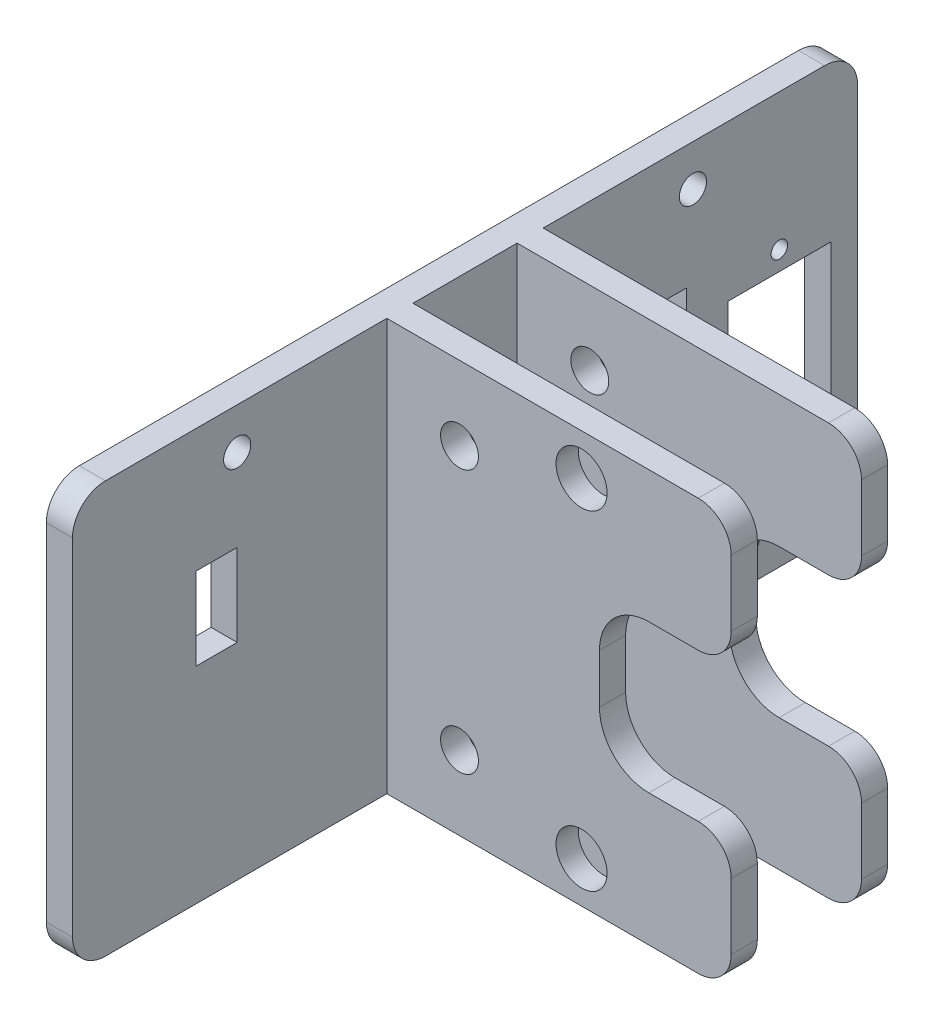
SolidWorks part; units mm, degrees
ref_plane "Front Plane" through (0, 0, 0) normal (0, 0, 1) x (1, 0, 0)
ref_plane "Top Plane" through (0, 0, 0) normal (0, 1, 0) x (1, 0, 0)
ref_plane "Right Plane" through (0, 0, 0) normal (1, 0, 0) x (0, 0, -1)
sketch "Sketch1" plane through (0, 0, 0) normal (0, 1, 0) x (1, 0, 0)
  line L0 (0, 9.5) -> (0, -9.5)
  line L5 (0, -9.5) -> (45, -9.5)
  line L6 (45, -9.5) -> (45, -6.325)
  line L17 (45, -6.325) -> (3.175, -6.325)
  line L18 (3.175, -6.325) -> (3.175, 6.325)
  line L19 (0, 0) -> (39.6882, 0) construction
  line L20 (45, 6.325) -> (3.175, 6.325)
  line L21 (45, 9.5) -> (45, 6.325)
  line L22 (0, 9.5) -> (45, 9.5)
  point P9 (3.175, 0)
  dimension "D1" = 19
  dimension "D2" = 3.175
  dimension "D3" = 3.175
  dimension "D4" = 45
extrude "Boss-Extrude1" add sketch "Sketch1" along normal blind 50
sketch "Sketch3" plane through (0, 0, 9.5) normal (0, 0, 1) x (1, 0, 0)
  line L1 (45, 50) -> (45, 0) construction
  line L2 (0, 50) -> (45, 50) construction
  line L3 (45, 25) -> (0, 25) construction
  line L4 (0, 50) -> (0, 0) construction
  circle A0 centre (26.825, 45) radius 3.1
  circle A2 centre (26.825, 5) radius 3.1
  dimension "D1" = 6.2
  dimension "D2" = 5
  dimension "D3" = 18.175
extrude "Cut-Extrude1" cut sketch "Sketch3" against normal blind 2.7
sketch "Sketch4" plane through (0, 0, -9.5) normal (0, 0, -1) x (-1, 0, 0)
  line L1 (-45, 50) -> (-45, 0) construction
  line L2 (0, 50) -> (-45, 50) construction
  line L3 (-45, 25) -> (0, 25) construction
  line L4 (0, 50) -> (0, 0) construction
  circle A0 centre (-26.825, 45) radius 3.1
  circle A2 centre (-26.825, 5) radius 3.1
  dimension "D4" = 6.2
  dimension "D1" = 5
  dimension "D2" = 18.175
extrude "Cut-Extrude2" cut sketch "Sketch4" against normal blind 2.7
fillet "Fillet1" radius 4 4 edges at (45, 50, 7.9125) (45, 50, -7.9125) (45, 0, -7.9125) (45, 0, 7.9125)
sketch "Sketch5" plane through (0, 0, 9.5) normal (0, 0, 1) x (1, 0, 0)
  line L0 (0, 25) -> (45, 25) construction
  line L1 (0, 50) -> (0, 0) construction
  line L2 (45, 46) -> (45, 4) construction
  circle A0 centre (12, 9) radius 2.3
  circle A1 centre (12, 41) radius 2.3
  dimension "D3" = 4.6
  dimension "D1" = 16
  dimension "D2" = 16
  dimension "D4" = 12
extrude "Cut-Extrude3" cut sketch "Sketch5" against normal up to surface (19 mm away) up to face at (23.725, 45, -9.5)
sketch "Sketch6" plane through (0, 0, 9.5) normal (0, 0, 1) x (1, 0, 0)
  line L0 (0, 0) -> (41, 0) construction
  line L1 (0, 50) -> (3.175, 50)
  line L2 (0, 50) -> (0, 0)
  line L3 (0, 0) -> (3.175, 0)
  line L4 (3.175, 50) -> (3.175, 0)
  dimension "D1" = 3.175
extrude "Boss-Extrude2" add sketch "Sketch6" along normal blind 38.175
sketch "Sketch7" plane through (0, 0, -9.5) normal (0, 0, -1) x (-1, 0, 0)
  line L0 (-41, 50) -> (0, 50) construction
  line L1 (0, 0) -> (-3.175, 0)
  line L2 (0, 0) -> (0, 50)
  line L3 (0, 50) -> (-3.175, 50)
  line L4 (-3.175, 0) -> (-3.175, 50)
  dimension "D1" = 3.175
extrude "Boss-Extrude3" add sketch "Sketch7" along normal blind 38.175
fillet "Fillet2" radius 4 4 edges at (1.5875, 0, -47.675) (1.5875, 50, -47.675) (1.5875, 0, 47.675) (1.5875, 50, 47.675)
sketch "Sketch10" plane through (0, 0, 0) normal (-1, 0, 0) x (0, 0, 1)
  line L0 (-47.675, 4) -> (-47.675, 46) construction
  line L3 (-43.675, 0) -> (43.675, 0) construction
  line L5 (-31.925, 31.075) -> (-44.425, 31.075)
  line L6 (-31.925, 31.075) -> (-31.925, 8.325)
  line L7 (-31.925, 8.325) -> (-44.425, 8.325)
  line L8 (-44.425, 31.075) -> (-44.425, 8.325)
  circle A0 centre (-38.175, 6) radius 1
  circle A1 centre (-38.175, 33.4) radius 1
  dimension "D1" = 2
  dimension "D2" = 27.4
  dimension "D3" = 9.5
  dimension "D4" = 6
  dimension "D5" = 12.5
  dimension "D6" = 22.75
  dimension "D7" = 2.325
  dimension "D8" = 6.25
extrude "Cut-Extrude7" cut sketch "Sketch10" against normal up to surface (3.175 mm away) up to face at (3.175, 25, -33.8928)
sketch "Sketch11" plane through (0, 0, 0) normal (-1, 0, 0) x (0, 0, 1)
  line L0 (-47.675, 25) -> (47.675, 25) construction
  line L1 (-47.675, 4) -> (-47.675, 46) construction
  line L2 (47.675, 46) -> (47.675, 4) construction
  line L3 (-43.675, 50) -> (43.675, 50) construction
  circle A2 centre (-27.675, 45) radius 1.65
  circle A3 centre (27.675, 45) radius 1.65
  circle A4 centre (-27.675, 5) radius 1.65
  dimension "D3" = 20
  dimension "D1" = 3.3
  dimension "D2" = 5
  dimension "D4" = 20
extrude "Cut-Extrude8" cut sketch "Sketch11" against normal up to surface (3.175 mm away) up to face at (3.175, 6, -37.175)
sketch "Sketch12" plane through (3.175, 0, 0) normal (1, 0, 0) x (0, 0, -1)
  line L0 (-43.675, 0) -> (-9.5, 0) construction
  line L1 (-32.675, 25) -> (-27.675, 25)
  line L2 (-32.675, 25) -> (-32.675, 35)
  line L3 (-32.675, 35) -> (-27.675, 35)
  line L4 (-27.675, 25) -> (-27.675, 35)
  line L5 (-47.675, 4) -> (-47.675, 46) construction
  line L6 (43.675, 0) -> (9.5, 0) construction
  line L7 (21.925, 25) -> (26.925, 25)
  line L8 (21.925, 25) -> (21.925, 35)
  line L9 (21.925, 35) -> (26.925, 35)
  line L10 (26.925, 25) -> (26.925, 35)
  line L11 (31.925, 31.075) -> (31.925, 8.325) construction
  dimension "D1" = 25
  dimension "D2" = 15
  dimension "D3" = 5
  dimension "D4" = 10
  dimension "D5" = 25
  dimension "D6" = 10
  dimension "D7" = 5
  dimension "D8" = 5
extrude "Cut-Extrude9" cut sketch "Sketch12" against normal up to surface (3.175 mm away) up to face at (0, 5, -29.325)
sketch "Sketch13" plane through (0, 0, 9.5) normal (0, 0, 1) x (1, 0, 0)
  line L0 (45, 46) -> (45, 4) construction
  line L1 (35, 16) -> (45, 16)
  line L2 (29, 22) -> (29, 28)
  line L3 (35, 34) -> (45, 34)
  line L4 (45, 16) -> (45, 34)
  line L5 (45, 25) -> (31.9606, 25) construction
  arc A0 (29, 28) -> (35, 34) centre (35, 28) cw
  arc A1 (35, 16) -> (29, 22) centre (35, 22) cw
  point P14 (29, 16)
  dimension "D3" = 6
  dimension "D1" = 18
  dimension "D2" = 16
extrude "Cut-Extrude10" cut sketch "Sketch13" against normal up to surface (19 mm away) up to face at (29.925, 5, -9.5)
fillet "Fillet3" radius 4 4 edges at (45, 16, -7.9125) (45, 16, 7.9125) (45, 34, 7.9125) (45, 34, -7.9125)
equation "\"D2@Sketch5\"=\"D1@Sketch5\""
equation "\"D7@Sketch10\"=(\"D2@Sketch10\"-\"D6@Sketch10\")/2"
equation "\"D8@Sketch10\"=\"D5@Sketch10\"/2"
equation "\"D5@Sketch12\"=\"D1@Sketch12\""
equation "\"D6@Sketch12\"=\"D4@Sketch12\""
equation "\"D7@Sketch12\"=\"D3@Sketch12\""
